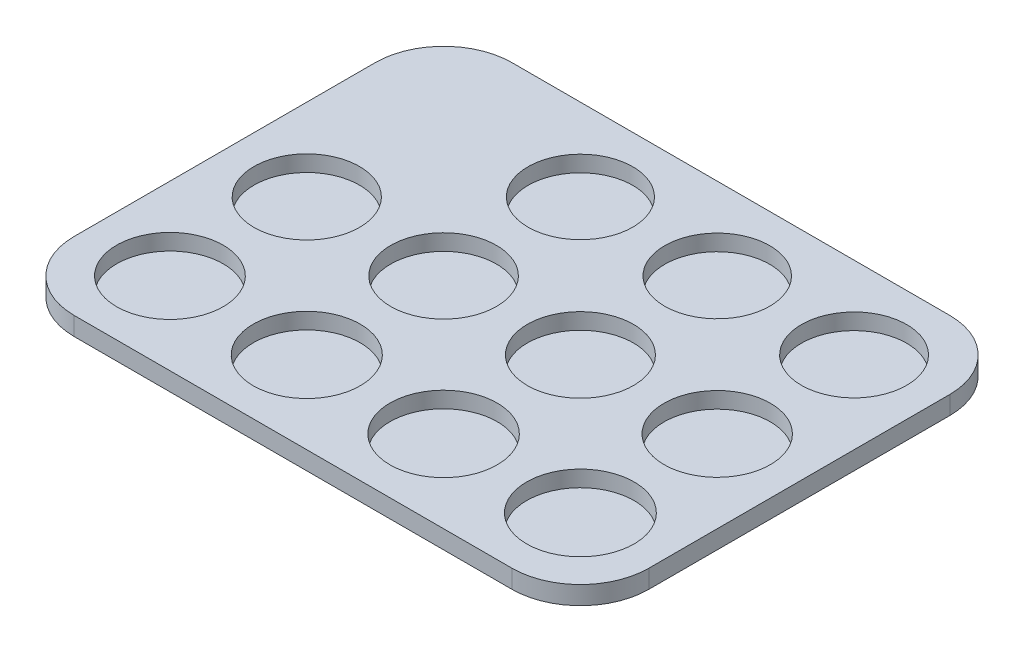
SolidWorks part; units mm, degrees
ref_plane "Front Plane" through (0, 0, 0) normal (0, 0, 1) x (1, 0, 0)
ref_plane "Top Plane" through (0, 0, 0) normal (0, 1, 0) x (1, 0, 0)
ref_plane "Right Plane" through (0, 0, 0) normal (1, 0, 0) x (0, 0, -1)
sketch "Sketch1" plane through (0, 0, 0) normal (0, 1, 0) x (1, 0, 0)
  line L1 (0, 0) -> (106.68, 0)
  line L2 (0, 0) -> (0, 81.28)
  line L3 (0, 81.28) -> (106.68, 81.28)
  line L4 (106.68, 0) -> (106.68, 81.28)
  circle A1 centre (15.24, 40.64) radius 9.8
  circle A2 centre (40.64, 40.64) radius 9.825
  circle A3 centre (66.04, 40.64) radius 9.85
  circle A4 centre (91.44, 40.64) radius 9.875
  circle A5 centre (15.24, 15.24) radius 9.9
  circle A6 centre (40.64, 15.24) radius 9.925
  circle A7 centre (66.04, 15.24) radius 9.95
  circle A8 centre (91.44, 15.24) radius 9.975
  circle A9 centre (91.44, 66.04) radius 9.775
  circle A10 centre (66.04, 66.04) radius 9.75
  circle A11 centre (40.64, 66.04) radius 9.725
  circle A12 centre (15.24, 66.04) radius 9.7 construction
  point P4 (15.24, 15.24)
  point P9 (40.64, 15.24)
  point P10 (66.04, 15.24)
  point P11 (91.44, 15.24)
  point P12 (40.64, 40.64)
  point P13 (66.04, 40.64)
  point P14 (91.44, 40.64)
  point P15 (15.24, 40.64)
  point P36 (15.24, 66.04)
  point P37 (40.64, 66.04)
  point P38 (66.04, 66.04)
  point P39 (91.44, 66.04)
  point P41 (16.2022, 40.6218)
  dimension "D1" = 4
  dimension "D3" = 19.95
  dimension "D4" = 19.9
  dimension "D5" = 19.85
  dimension "D6" = 19.8
  dimension "D7" = 19.75
  dimension "D8" = 19.7
  dimension "D9" = 19.65
  dimension "D10" = 19.6
  dimension "D11" = 19.55
  dimension "D12" = 19.5
  dimension "D13" = 19.45
  dimension "D14" = 19.4
  dimension "D2" = 3
  dimension "D15" = 25.4
  dimension "D16" = 25.4
  dimension "D17" = 15.24
  dimension "D18" = 15.24
  dimension "D19" = 15.24
  dimension "D20" = 15.24
extrude "Boss-Extrude1" add sketch "Sketch1" along normal blind 3
extrude "Boss-Extrude2" add sketch "Sketch1<2>" against normal blind 0.4 contours A5 | A1 | A6 | A2 | A7 | A3 | L1 L4 L3 L2 A12 A11 A10 A9 A8 A7 A6 A5 A4 A3 A2 A1 | A8 | A4 | A9 | A10 | A11 | A12 region at (51.1115, 0, -42.288) region at (15.24, 0, -40.64) region at (40.64, 0, -40.64) region at (66.04, 0, -40.64) region at (91.44, 0, -40.64) region at (15.24, 0, -15.24) region at (40.64, 0, -15.24) region at (66.04, 0, -15.24) region at (91.44, 0, -15.24) region at (91.44, 0, -66.04) region at (66.04, 0, -66.04) region at (40.64, 0, -66.04)
sketch "Sketch1<2>" plane through (0, 0, 0) normal (0, 1, 0) x (1, 0, 0) same geometry as "Sketch1"
fillet "Fillet1" radius 12.7 4 edges at (0, 1.3, -81.28) (106.68, 1.3, -81.28) (106.68, 1.3, 0) (0, 1.3, 0)
